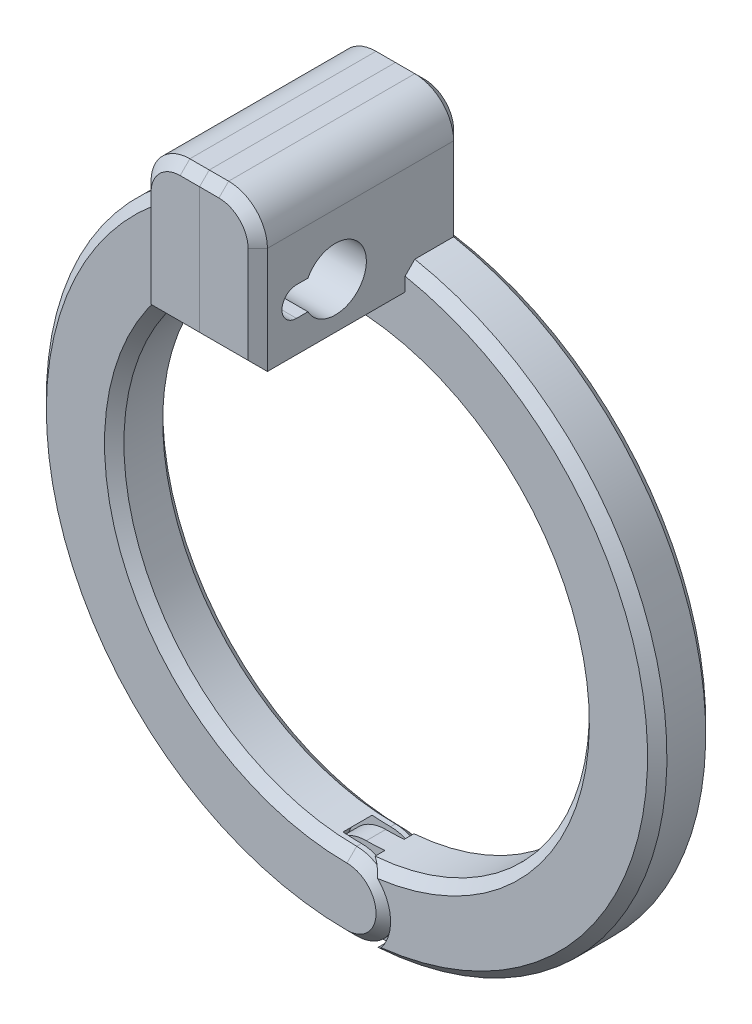
SolidWorks part; units mm, degrees
ref_plane "Ebene vorne" through (0, 0, 0) normal (0, 0, 1) x (1, 0, 0)
ref_plane "Ebene oben" through (0, 0, 0) normal (0, 1, 0) x (1, 0, 0)
ref_plane "Ebene rechts" through (0, 0, 0) normal (1, 0, 0) x (0, 0, -1)
sketch "Skizze1" plane through (0, 0, 0) normal (0, 0, 1) x (1, 0, 0)
  line L1 (0, -32) -> (0, -8) construction
  line L2 (0, -8) -> (0, 0)
  arc A0 (0, -8) -> (0, -56) centre (0, -32) ccw
  arc A1 (0, -56) -> (0, -64) centre (0, -60) cw
  arc A2 (0, -64) -> (0, 0) centre (0, -32) cw
  dimension "D1" = 4
  dimension "D2" = 24
extrude "Aufsatz-Linear austragen1" add sketch "Skizze1" along normal mid plane 6
sketch "Skizze2" plane through (0, 0, 0) normal (0, 0, 1) x (1, 0, 0)
  circle A0 centre (0, -60) radius 4.5
  dimension "D1" = 9
extrude "Schnitt-Linear austragen1" cut sketch "Skizze2" against normal mid plane 3
sketch "Skizze3" plane through (0, 0, 0) normal (0, 0, 1) x (1, 0, 0)
  circle A0 centre (0, -60) radius 2
  dimension "D1" = 4
extrude "Aufsatz-Linear austragen2" add sketch "Skizze3" along normal up to surface and the other way up to surface up to face at (-0.6383, -59.949, 1.5) other way up to face at (-0.6383, -59.949, -1.5)
sketch "Skizze4" plane through (0, 0, 0) normal (0, 0, 1) x (1, 0, 0)
  line L0 (0, -32) -> (0, -8) construction
  line L1 (0, -8) -> (0, 0)
  arc A0 (0, -8) -> (0, -56) centre (0, -32) cw
  arc A1 (0, 0) -> (0, -64) centre (0, -32) cw
  arc A2 (0, -56) -> (0, -64) centre (0, -60) ccw
  arc A3 (0, -8) -> (0, -56) centre (0, -32) ccw construction
  arc A4 (0, 0) -> (0, -64) centre (0, -32) ccw construction
  circle A5 centre (0, -60) radius 2.5
  dimension "D2" = 5
extrude "Aufsatz-Linear austragen4" add sketch "Skizze4" along normal mid plane 6 separate body
sketch "Skizze5" plane through (0, 0, 3) normal (0, 0, 1) x (1, 0, 0)
  circle A0 centre (0, -60) radius 4.5
  dimension "D1" = 9
extrude "Schnitt-Linear austragen2" cut sketch "Skizze5" against normal blind 2
mirror "Spiegeln1" about plane through (0, 0, 0) normal (0, 0, 1) of "Schnitt-Linear austragen2"
sketch "Skizze6" plane through (0, 0, -3) normal (0, 0, -1) x (-1, 0, 0)
  line L0 (0, 0) -> (0, 12)
  line L1 (0, 0) -> (0, -8) construction
  line L2 (0, 12) -> (-2, 12)
  line L3 (-6, 8) -> (-6, -0.5675)
  arc A0 (-2, 12) -> (-6, 8) centre (-2, 8) ccw
  arc A1 (0, 0) -> (-2.2026, -63.9241) centre (0, -32) ccw construction
  arc A2 (0, 0) -> (-6, -0.5675) centre (0, -32) ccw
  dimension "D1" = 6
  dimension "D2" = 2
  dimension "D3" = 12
extrude "Aufsatz-Linear austragen5" add sketch "Skizze6" against normal up to surface (6 mm away) up to face at (15.1147, -31.4444, 3)
sketch "Skizze7" plane through (0, 0, -3) normal (0, 0, -1) x (-1, 0, 0)
  line L0 (0, 0) -> (0, 12)
  line L1 (0, 12) -> (2, 12)
  line L2 (6, 8) -> (6, -0.5675)
  line L3 (0, -8) -> (0, 0) construction
  arc A0 (2, 12) -> (6, 8) centre (2, 8) cw
  arc A1 (0, -64) -> (0, 0) centre (0, -32) ccw construction
  arc A2 (6, -0.5675) -> (0, 0) centre (0, -32) ccw
  dimension "D1" = 2
  dimension "D2" = 12
  dimension "D3" = 6
extrude "Aufsatz-Linear austragen6" add sketch "Skizze7" against normal up to surface (6 mm away) up to face at (-13, -32, 3)
sketch "Skizze8" plane through (0, 0, 3) normal (0, 0, 1) x (1, 0, 0)
  line L0 (0, -3) -> (6, -3)
  line L3 (6, -0.5675) -> (6, 8)
  line L4 (2, 12) -> (0, 12)
  line L5 (0, 12) -> (0, -8)
  line L6 (6, -3) -> (6, 8)
  line L7 (2, 12) -> (0, 12)
  line L8 (0, 12) -> (0, -3)
  arc A4 (1.9071, -55.9241) -> (0, -8) centre (0, -32) ccw
  arc A5 (2.2026, -63.9241) -> (1.9071, -55.9241) centre (0, -60) ccw
  arc A6 (2.2026, -63.9241) -> (6, -0.5675) centre (0, -32) ccw
  arc A7 (6, 8) -> (2, 12) centre (2, 8) ccw
  arc A11 (6, 8) -> (2, 12) centre (2, 8) ccw
  dimension "D2" = 15
  dimension "D1" = 0
extrude "Aufsatz-Linear austragen7" add sketch "Skizze8" along normal blind 15.2
sketch "Skizze9" plane through (0, 0, 3) normal (0, 0, 1) x (1, 0, 0)
  line L2 (0, -3) -> (-6, -3)
  line L5 (0, -8) -> (0, 12)
  line L6 (0, 12) -> (-2, 12)
  line L14 (-6, 8) -> (-6, -0.5675)
  line L15 (0, -3) -> (0, 12)
  line L16 (0, 12) -> (-2, 12)
  line L17 (-6, 8) -> (-6, -3)
  arc A4 (0, -8) -> (0, -56) centre (0, -32) ccw
  arc A5 (-2, 12) -> (-6, 8) centre (-2, 8) ccw
  arc A6 (-6, -0.5675) -> (0, -64) centre (0, -32) ccw
  arc A7 (0, -64) -> (0, -56) centre (0, -60) ccw
  arc A16 (0, -8) -> (0, -56) centre (0, -32) ccw
  arc A17 (-2, 12) -> (-6, 8) centre (-2, 8) ccw
  line M10 (0, -8) -> (0, 12)
  line M12 (0, 12) -> (-2, 12)
  arc M13 (-2, 12) -> (-6, 8) centre (-2, 8) ccw
  line M14 (-6, 8) -> (-6, -0.5675)
  dimension "D2" = 15
  dimension "D1" = 0
extrude "Aufsatz-Linear austragen9" add sketch "Skizze9" along normal up to surface (15.2 mm away) contours L2 M10 M12 M13 M14 region at (-2.9164, 4.238, 3) up to face at (2.9657, 5.3657, 18.2)
sketch "Skizze10" plane through (0, 0, 0) normal (1, 0, 0) x (0, 0, -1)
  line L0 (-18.2, -3) -> (-18.2, 8) construction
  line L1 (-18.2, -3) -> (-3, -3) construction
  line L2 (-10.2, 1.75) -> (-14.2, 1.75) construction
  line L3 (-13.0267, 3.25) -> (-14.2, 3.25)
  line L4 (-13.0267, 0.25) -> (-14.2, 0.25)
  circle A0 centre (-10.2, 1.75) radius 3.2
  arc A1 (-14.2, 3.25) -> (-14.2, 0.25) centre (-14.2, 1.75) ccw
  dimension "D1" = 6.4
  dimension "D5" = 1.5
  dimension "D2" = 8
  dimension "D3" = 4.75
  dimension "D4" = 4
extrude "Schnitt-Linear austragen3" cut sketch "Skizze10" against normal mid plane 13 contours A0 | L3 A1 L4 A0 region at (0, 1.75, 14.3522) region at (0, 1.75, 10.2)
chamfer "Fase1" distance 1 angle 45 2 edges at (23.981, -31.0457, 3) (23.981, -31.0457, -3)
chamfer "Fase2" distance 1 angle 45 2 edges at (-24, -32, 3) (-24, -32, -3) tangent propagation no
chamfer "Fase3" distance 1 angle 45 5 edges at (31.9427, -33.9146, 3) (31.9427, -33.9146, -3) (1, 12, -3) (4.8284, 10.8284, -3) (6, 3.7162, -3)
chamfer "Fase4" distance 1 angle 45 7 edges at (-31.8578, -35.0134, 3) (-31.8578, -35.0134, -3) (3.7749, -61.3229, 3) (-1, 12, -3) (-4.8284, 10.8284, -3) (3.7749, -61.3229, -3) (-6, 3.7162, -3)
chamfer "Fase5" distance 1 angle 45 4 edges at (1, 12, 18.2) (4.8284, 10.8284, 18.2) (3, -3, 18.2) (6, 2.5, 18.2)
chamfer "Fase6" distance 1 angle 45 4 edges at (-1, 12, 18.2) (-3, -3, 18.2) (-6, 2.5, 18.2) (-4.8284, 10.8284, 18.2)
